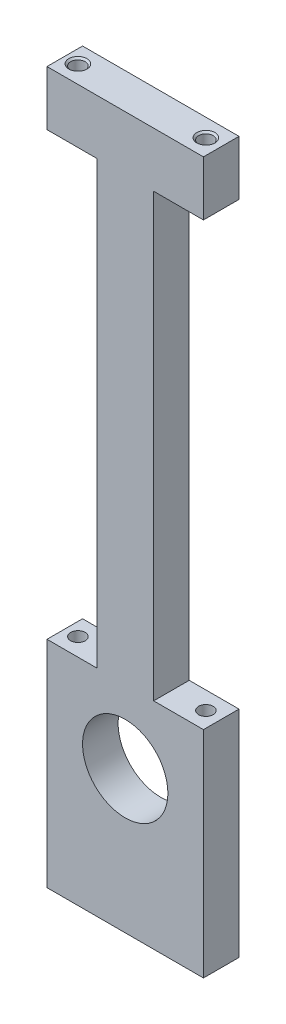
SolidWorks part; units mm, degrees
material "6061 合金"
ref_plane "前视基准面" through (0, 0, 0) normal (0, 0, 1) x (1, 0, 0)
ref_plane "上视基准面" through (0, 0, 0) normal (0, 1, 0) x (1, 0, 0)
ref_plane "右视基准面" through (0, 0, 0) normal (1, 0, 0) x (0, 0, -1)
sketch "草图1" plane through (0, 0, 0) normal (0, 0, 1) x (1, 0, 0)
  line L0 (-6, 0) -> (-11, 0)
  line L1 (-11, 0) -> (-11, 10.2507)
  line L2 (-11, 10.2507) -> (11, 10.2507)
  line L3 (11, 10.2507) -> (11, 0)
  line L4 (11, 0) -> (6, 0)
  line L5 (0, 6) -> (0, 10.2507) construction
  arc A0 (6, 0) -> (-6, 0) centre (0, 0) ccw
  dimension "D2" = 6
  dimension "D1" = 22
extrude "凸台-拉伸1" add sketch "草图1" along normal blind 5
sketch "草图2" plane through (0, 0, 5) normal (0, 0, 1) x (1, 0, 0)
  line L0 (11, 10.2507) -> (-11, 10.2507) construction
  line L1 (0, 80) -> (0, 41.2809) construction
  line L2 (4, 72.3111) -> (4, 10.2507)
  line L3 (4, 10.2507) -> (-4, 10.2507)
  line L4 (-4, 72.3111) -> (-4, 10.2507)
  line L5 (4, 72.3111) -> (-4, 10.2507) construction
  line L6 (4, 10.2507) -> (-4, 72.3111) construction
  line L7 (0, 6) -> (0, 10.2507) construction
  line L8 (-4, 72.3111) -> (-11, 72.3111)
  line L9 (-11, 72.3111) -> (-11, 80)
  line L10 (-11, 80) -> (11, 80)
  line L11 (11, 80) -> (11, 72.3111)
  line L12 (11, 72.3111) -> (4, 72.3111)
  line L13 (-11, 0) -> (-6, 0) construction
  line L14 (11, 10.2507) -> (11, 0) construction
  arc A0 (6, 0) -> (-6, 0) centre (0, 0) ccw construction
  point P0 (0, 41.2809)
  dimension "D1" = 8
  dimension "D3" = 80
extrude "凸台-拉伸2" add sketch "草图2" against normal up to surface (5 mm away) up to face at (0, 4.4169, 0)
sketch "草图3" plane through (0, 80, 0) normal (0, 1, 0) x (1, 0, 0)
  line L0 (-11, -2.5) -> (11, -2.5) construction
  line L1 (-11, 0) -> (-11, -5) construction
  line L2 (11, 0) -> (11, -5) construction
  line L3 (0, -2.5) -> (0, 0) construction
  line L4 (-11, 0) -> (11, 0) construction
  point P6 (-9.1547, -2.5)
  point P7 (8.8453, -2.5)
  dimension "D1" = 18
sketch "草图6" plane through (0, 0, 0) normal (0, 0, -1) x (-1, 0, 0)
  line L1 (-11, -10) -> (11, -10)
  line L2 (-11, 10.2507) -> (-11, -10)
  line L3 (11, 80) -> (-11, 80) construction
  line L4 (11, -10) -> (11, 10.2507)
  line L5 (11, 10.2507) -> (-11, 10.2507)
  circle A0 centre (0, 0) radius 6
  arc A1 (6, 0) -> (-6, 0) centre (0, 0) ccw construction
  dimension "D1" = 90
extrude "凸台-拉伸3" add sketch "草图6" against normal up to surface (5 mm away) up to face at (0, 35.4462, 5)
hole_wizard "M2.5 螺纹孔1" positions "草图4" profile "草图5" tap size "M2.5" standard "GB" end condition through all
sketch "草图4" plane through (0, 80, 0) normal (0, 1, 0) x (1, 0, 0)
  point P0 (-9.1547, -2.5)
  point P3 (8.8453, -2.5)
cosmetic thread "孔螺蚊线1" parameters "D2"=2.5
cosmetic thread "孔螺蚊线2" parameters "D2"=2.5
sketch "草图5" plane through (-9.1547, 80, 2.5) normal (1, 0, 0) x (0, 0, 1)
  line L0 (0, 0) -> (0, 90)
  line L1 (0, 90) -> (1.025, 90)
  line L2 (1.025, 90) -> (1.025, 0.25)
  line L3 (1.025, 0.25) -> (1.275, 0)
  line L5 (1.275, 0) -> (0, 0)
  line L6 (-1.025, 0.25) -> (-1.275, 0) construction
  line L11 (0, -6.35) -> (0, 107.95) construction
  dimension "通孔螺纹孔钻头直径" = 2.05
  dimension "通孔螺纹孔钻头深度" = 90
  dimension "近端锥形沉头孔直径" = 2.55
  dimension "近端锥形沉头孔角度" = 90
sketch "草图7" plane through (0, 0, 5) normal (0, 0, 1) x (1, 0, 0)
  line L0 (11, -10) -> (11, 10.2507) construction
  line L1 (-11, -10) -> (11, -10)
  line L2 (-11, -10) -> (-11, -20)
  line L3 (-11, -20) -> (11, -20)
  line L4 (11, -10) -> (11, -20)
  point P7 (11, -15)
  dimension "D1" = 10
extrude "凸台-拉伸4" add sketch "草图7" against normal up to surface (5 mm away) up to face at (0, 39.1873, 0)
